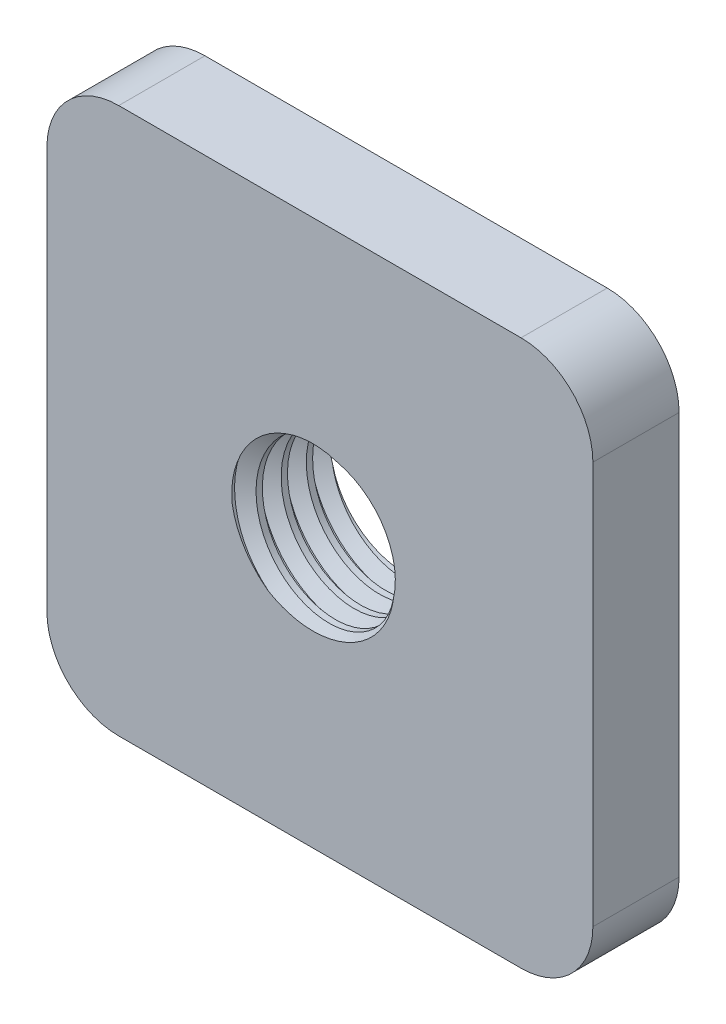
SolidWorks part; units mm, degrees
material "1.0037 (S235JR)"
ref_plane "Front Plane" through (0, 0, 0) normal (0, 0, 1) x (1, 0, 0)
ref_plane "Top Plane" through (0, 0, 0) normal (0, 1, 0) x (1, 0, 0)
ref_plane "Right Plane" through (0, 0, 0) normal (1, 0, 0) x (0, 0, -1)
sketch "Sketch1" plane through (0, 0, 0) normal (0, 0, 1) x (1, 0, 0)
  line L1 (-5, 0) -> (-33, 0)
  line L2 (0, 5) -> (0, 33)
  line L3 (-5, 38) -> (-33, 38)
  line L4 (-38, 5) -> (-38, 33)
  arc A1 (-33, 0) -> (-38, 5) centre (-33, 5) cw
  arc A2 (-5, 0) -> (0, 5) centre (-5, 5) ccw
  arc A3 (0, 33) -> (-5, 38) centre (-5, 33) ccw
  arc A4 (-33, 38) -> (-38, 33) centre (-33, 33) ccw
  circle A5 centre (-19, 19) radius 5.25
  point P11 (0, 0)
  point P14 (0, 38)
  point P17 (-38, 38)
  dimension "D5" = 10.5
  dimension "D6" = 5
  dimension "D4" = 19
  dimension "D1" = 38
  dimension "D2" = 38
  dimension "D3" = 19
extrude "Boss-Extrude1" add sketch "Sketch1" along normal blind 6
thread "Thread1" pitch 1.75 method cut profile "Thread Profile1" start angle 0, offset 4, length 20, pitch 1.75, diameter 10.5
ref_plane "Plane1" through (-24.25, 19, 10) normal (0, -1, 0) x (-1, 0, 0)
sketch "Thread Profile1" plane through (-24.25, 19, 10) normal (0, -1, 0) x (-1, 0, 0)
  line L0 (0, 0) -> (0, 1.75) construction
  line L1 (0, 0) -> (0.9472, 0.5469)
  line L2 (0.9472, 0.5469) -> (0.9472, 0.7656)
  line L3 (0.9472, 0.7656) -> (0, 1.3125)
  line L4 (0.9472, 0.6562) -> (0, 0.6562) construction
  line L11 (0, 0) -> (0, 1.3125)
  point P2 (0, 0)
  dimension "Pitch" = 1.75
  dimension "Profile_Angle" = 60
  dimension "Profile_Land" = 0.2188
  dimension "Profile_Height" = 0.9472
